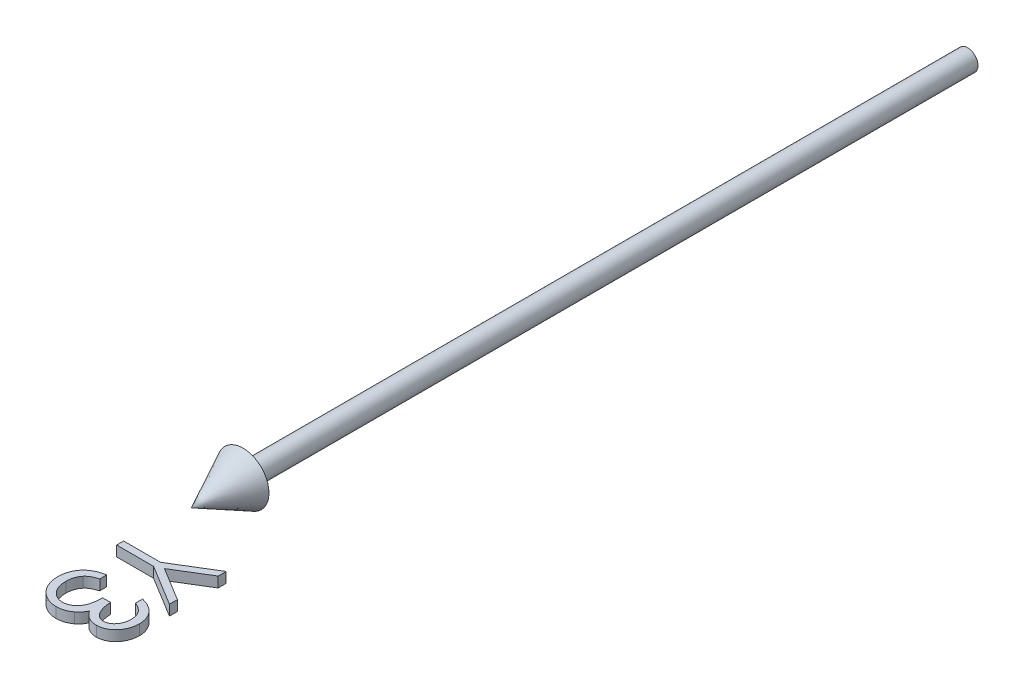
SolidWorks part; units mm, degrees
ref_plane "Front Plane" through (0, 0, 0) normal (0, 0, 1) x (1, 0, 0)
ref_plane "Top Plane" through (0, 0, 0) normal (0, 1, 0) x (1, 0, 0)
ref_plane "Right Plane" through (0, 0, 0) normal (1, 0, 0) x (0, 0, -1)
sketch "Sketch2" plane through (0, 0, 0) normal (0, 1, 0) x (1, 0, 0)
  line L0 (0, 41.95) -> (0, -114.4521) construction
  line L1 (-36.8894, 0) -> (41.4965, 0) construction
  line L2 (0, -150) -> (5, -140)
  line L3 (5, -140) -> (2, -140)
  line L4 (2, -140) -> (2, 0)
  line L5 (2, 0) -> (0, 0)
  line L6 (0, 0) -> (0, -150)
  dimension "D1" = 150
  dimension "D2" = 2
  dimension "D3" = 10
  dimension "D4" = 5
revolve "Revolve1" add sketch "Sketch2" angle 360 about L0
sketch "Sketch3" plane through (0, 0, 0) normal (0, 1, 0) x (1, 0, 0)
  line L0 (0, -157.5) -> (0, -264.219) construction
  line L1 (-28.4966, 0) -> (36.1227, 0) construction
  text T0 "Y3\r\n" font "Century Gothic" height 15
  dimension "D1" = 157.5
extrude "Boss-Extrude1" add sketch "Sketch3" against normal blind 1 and the other way blind 1 separate body
equation "\"D1@Sketch2\"=\"frame_arrow_length\""
equation "\"D2@Sketch2\"=\"frame_arrow_odA\"/2"
equation "\"D4@Sketch2\"=\"frame_arrow_head_od\""
equation "\"D3@Sketch2\"=\"frame_arrow_head_length\""
equation "\"frame_arrow_length\"=150"
equation "\"frame_arrow_head_length\"=10"
equation "\"frame_arrow_head_od\"=5"
equation "\"frame_arrow_odA\"=4"
equation "\"D1@Sketch3\"=\"frame_arrow_length\"*1.05"
